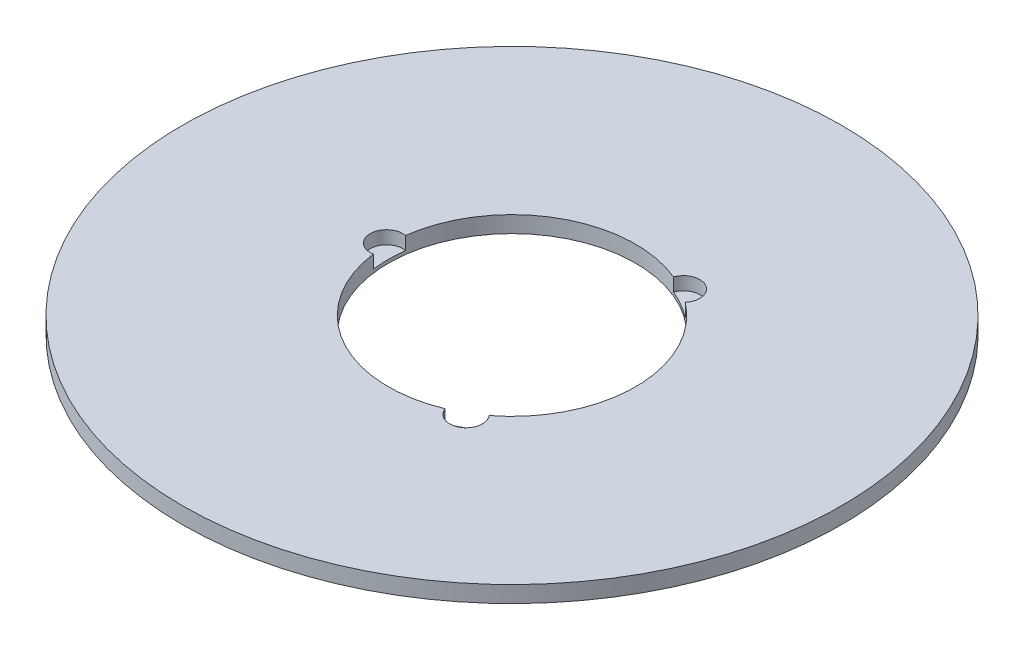
SolidWorks part; units mm, degrees
ref_plane "Front Plane" through (0, 0, 0) normal (0, 0, 1) x (1, 0, 0)
ref_plane "Top Plane" through (0, 0, 0) normal (0, 1, 0) x (1, 0, 0)
ref_plane "Right Plane" through (0, 0, 0) normal (1, 0, 0) x (0, 0, -1)
sketch "Sketch1" plane through (0, 0, 0) normal (0, 1, 0) x (1, 0, 0)
  circle A0 centre (0, 0) radius 80
  dimension "FLANGE_OD" = 160
extrude "Boss-Extrude1" add sketch "Sketch1" along normal blind 4
sketch "Sketch2" plane through (0, 0, 0) normal (0, 1, 0) x (1, 0, 0)
  circle A0 centre (0, 0) radius 30
  dimension "BORE_D" = 60
extrude "Cut-Extrude1" cut sketch "Sketch2" along normal through all
sketch "Sketch3" plane through (0, 4, 0) normal (0, 1, 0) x (1, 0, 0)
  circle A0 centre (0, 0) radius 30.4586 construction
  circle A1 centre (-30.4586, 0) radius 3.969
  dimension "BOLT_D" = 7.938
  dimension "BOLT_PCD" = 60.9173
extrude "Cut-Extrude2" cut sketch "Sketch3" against normal blind 3.1837
pattern_circular "CirPattern1" count 3 over 360 about axis through (0, 0, 0) along (0, 1, 0) of "Cut-Extrude2"
